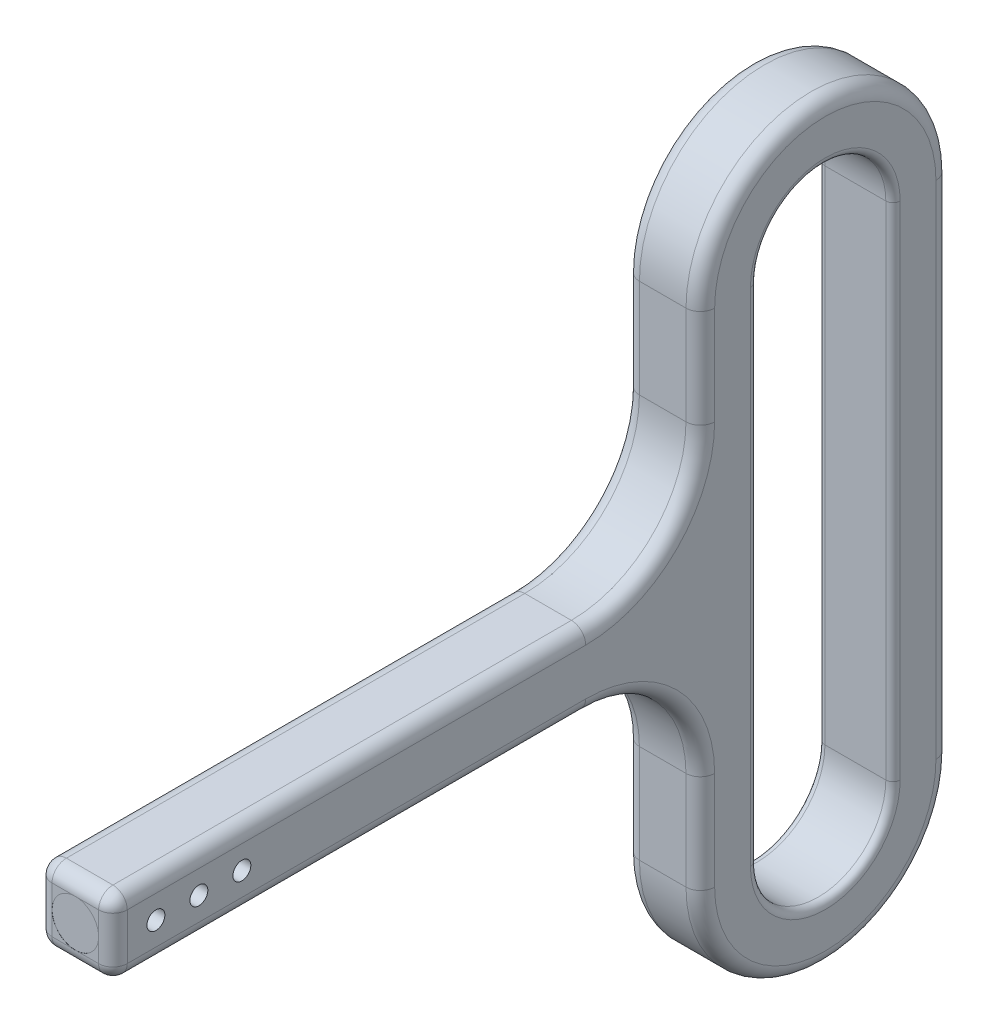
SolidWorks part; units mm, degrees
ref_plane "Front Plane" through (0, 0, 0) normal (0, 0, 1) x (1, 0, 0)
ref_plane "Top Plane" through (0, 0, 0) normal (0, 1, 0) x (1, 0, 0)
ref_plane "Right Plane" through (0, 0, 0) normal (1, 0, 0) x (0, 0, -1)
sketch "Sketch2" plane through (0, 0, 0) normal (1, 0, 0) x (0, 0, -1)
  line L0 (-22.16, -44.45) -> (-22.16, 44.45)
  line L1 (0, -44.45) -> (0, 44.45) construction
  line L2 (-12, -44.45) -> (-12, 44.45)
  line L3 (12, -44.45) -> (12, 44.45)
  line L4 (22.16, -44.45) -> (22.16, 44.45)
  line L5 (0, 0) -> (-80.0365, 0) construction
  line L6 (-22.16, -6.6675) -> (-126.3, -6.6675)
  line L7 (-22.16, 0) -> (-126.3, 0) construction
  line L8 (-22.16, 0) -> (-22.16, 6.6675)
  line L9 (-22.16, 6.6675) -> (-126.3, 6.6675)
  line L10 (-126.3, -6.6675) -> (-126.3, 6.6675)
  line L11 (-126.3, 0) -> (-118.68, 0) construction
  arc A0 (-12, -44.45) -> (12, -44.45) centre (0, -44.45) ccw
  arc A1 (12, 44.45) -> (-12, 44.45) centre (0, 44.45) ccw
  arc A2 (22.16, 44.45) -> (-22.16, 44.45) centre (0, 44.45) ccw
  arc A3 (-22.16, -44.45) -> (22.16, -44.45) centre (0, -44.45) ccw
  circle A4 centre (-118.68, 0) radius 1.5875
  circle A6 centre (-111.06, 0) radius 1.5875
  circle A7 centre (-103.44, 0) radius 1.5875
  point P5 (0, 0)
  point P16 (-40.0182, 0)
  dimension "D2" = 12
  dimension "D7" = 3.175
  dimension "D1" = 88.9
  dimension "D4" = 104.14
  dimension "D5" = 13.335
  dimension "D6" = 7.62
  dimension "D3" = 10.16
  dimension "D8" = 3
extrude "Boss-Extrude2" add sketch "Sketch2" along normal blind 13.335 contours L10 L6 L0 L9 | L0 A3 L4 A2 A1 L3 A0 L2 region at (0, -25.5588, 20.756) region at (0, 0, 73.5891)
sketch "Sketch3" plane through (0, 0, 126.3) normal (0, 0, 1) x (1, 0, 0)
  line L0 (0, 0) -> (13.335, 0) construction
  line L1 (0, -6.6675) -> (0, 6.6675) construction
  line L2 (13.335, -6.6675) -> (13.335, 6.6675) construction
  line L7 (0, 6.6675) -> (0, -6.6675)
  line L8 (0, -6.6675) -> (13.335, -6.6675)
  line L9 (13.335, -6.6675) -> (13.335, 6.6675)
  line L10 (13.335, 6.6675) -> (0, 6.6675)
  line L11 (0, 6.6675) -> (0, -6.6675)
  line L12 (0, -6.6675) -> (13.335, -6.6675)
  line L13 (13.335, -6.6675) -> (13.335, 6.6675)
  line L14 (13.335, 6.6675) -> (0, 6.6675)
  circle A1 centre (-0.3175, 0) radius 13.6525 construction
  circle A2 centre (-0.3175, 0) radius 8.89
  dimension "D1" = 27.305
  dimension "D3" = 17.78
  dimension "D2" = 0
extrude "Cut-Extrude3" [suppressed] cut sketch "Sketch3" against normal blind 16.51
sketch "Sketch4" plane through (0, 0, 0) normal (-1, 0, 0) x (0, 0, 1)
  line L1 (-69.1853, 78.6449) -> (69.1853, 78.6449)
  line L2 (-69.1853, 78.6449) -> (-69.1853, -78.6449)
  line L3 (-69.1853, -78.6449) -> (69.1853, -78.6449)
  line L4 (69.1853, 78.6449) -> (69.1853, -78.6449)
  line L5 (-69.1853, 78.6449) -> (69.1853, -78.6449) construction
  line L6 (-69.1853, -78.6449) -> (69.1853, 78.6449) construction
  point P0 (0, 0)
extrude "Cut-Extrude4" [suppressed] cut sketch "Sketch4" against normal blind 8.89
chamfer "Chamfer1" [suppressed] distance 10 angle 74
sketch "Sketch6" plane through (0, 0, 126.3) normal (0, 0, 1) x (1, 0, 0)
  line L0 (13.335, 0) -> (0, 0) construction
  line L1 (13.335, -6.6675) -> (13.335, 6.6675) construction
  line L2 (0, -6.6675) -> (0, 6.6675) construction
  circle A0 centre (6.6675, 0) radius 6.6675 construction
fillet "Fillet4" radius 2.54 2 edges at (6.6675, -6.6675, 126.3) (6.6675, 6.6675, 126.3)
fillet "Fillet2" radius 20.32 2 edges at (6.6675, -6.6675, 22.16) (6.6675, 6.6675, 22.16)
fillet "Fillet1" radius 2.54 24 edges at (13.335, 6.6675, 83.12) (0, 6.6675, 83.12) (13.335, -6.6675, 83.12) (0, -6.6675, 83.12) (13.335, 35.7187, 22.16) (13.335, 66.61, 0) (13.335, 0, -22.16) (13.335, -66.61, 0) (0, 35.7187, 22.16) (0, 66.61, 0) (0, 0, -22.16) (0, -66.61, 0) (13.335, -35.7188, 22.16) (0, -35.7188, 22.16) (13.335, 12.6191, 28.1116) (13.335, -12.6191, 28.1116) (0, 12.6191, 28.1116) (0, -12.6191, 28.1116) (13.335, 5.9236, 125.5561) (13.335, 0, 126.3) (13.335, -5.9236, 125.5561) (0, 5.9236, 125.5561) (0, 0, 126.3) (0, -5.9236, 125.5561)
fillet "Fillet3" radius 1.27 8 edges at (0, -56.45, 0) (0, 0, -12) (0, 56.45, 0) (13.335, -56.45, 0) (13.335, 0, -12) (13.335, 56.45, 0) (0, 0, 12) (13.335, 0, 12)
sketch "Sketch7" plane through (0, 0, 126.3) normal (0, 0, 1) x (1, 0, 0)
  circle A0 centre (6.6675, 0) radius 4.1275
extrude "Cut-Extrude6" cut sketch "Sketch7" against normal blind 0.0127
